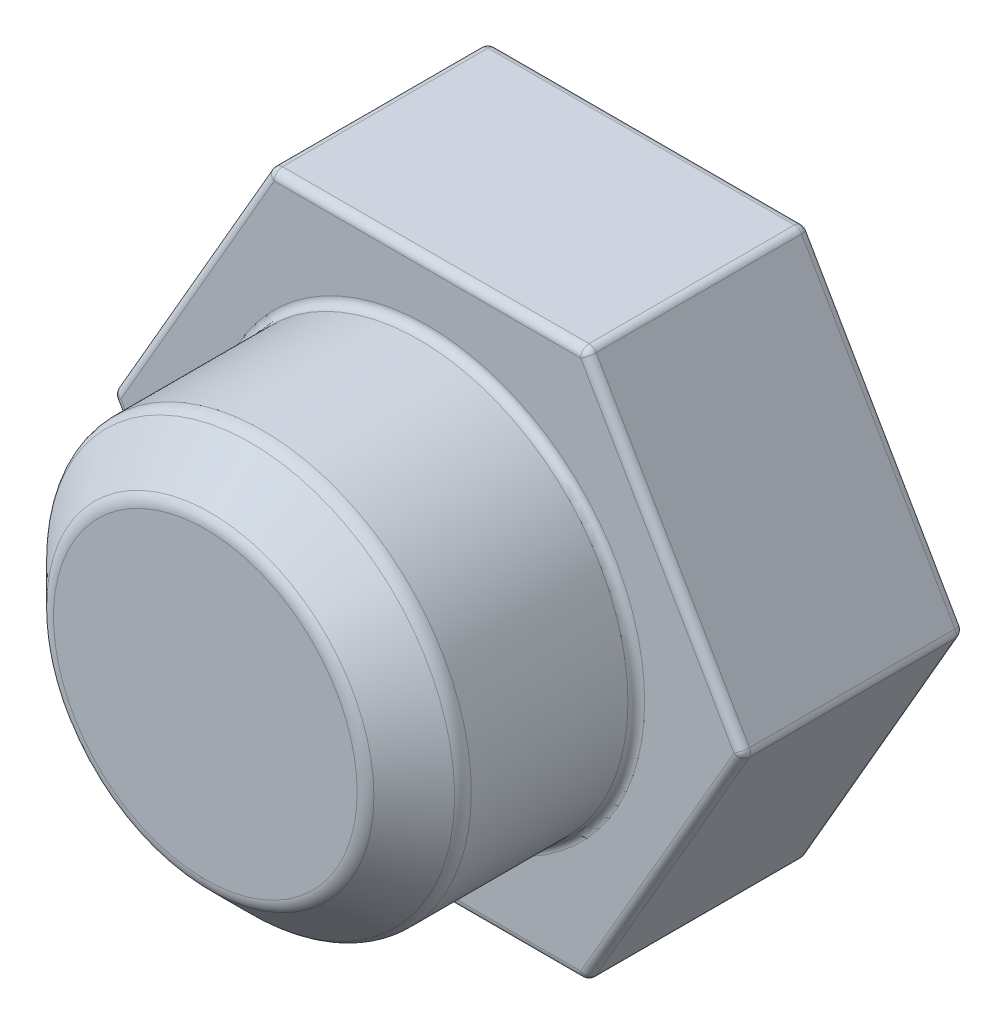
SolidWorks part; units mm, degrees
material "moto_black"
ref_plane "Front Plane" through (0, 0, 0) normal (0, 0, 1) x (1, 0, 0)
ref_plane "Top Plane" through (0, 0, 0) normal (0, 1, 0) x (1, 0, 0)
ref_plane "Right Plane" through (0, 0, 0) normal (1, 0, 0) x (0, 0, -1)
sketch "Sketch1" plane through (0, 0, 0) normal (0, 0, 1) x (1, 0, 0)
  line L1 (18.9181, 0) -> (9.459, 16.3835)
  line L2 (9.459, 16.3835) -> (-9.459, 16.3835)
  line L3 (-9.459, 16.3835) -> (-18.9181, 0)
  line L4 (-18.9181, 0) -> (-9.459, -16.3835)
  line L5 (-9.459, -16.3835) -> (9.459, -16.3835)
  line L6 (9.459, -16.3835) -> (18.9181, 0)
  circle A0 centre (0, 0) radius 16.3835 construction
  circle A1 centre (0, 0) radius 12.5
  dimension "D1" = 25
extrude "Boss-Extrude1" add sketch "Sketch1" against normal blind 13.29
sketch "Sketch2" plane through (0, 0, 0) normal (0, 0, 1) x (1, 0, 0)
  circle A0 centre (0, 0) radius 12.5
  dimension "D1" = 25
extrude "Boss-Extrude2" add sketch "Sketch2" against normal blind 13
extrude "Boss-Extrude3" add sketch "Sketch2<2>" along normal blind 13.29
sketch "Sketch2<2>" plane through (0, 0, 0) normal (0, 0, 1) x (1, 0, 0) same geometry as "Sketch2"
chamfer "Chamfer1" distance 3 angle 45 1 edges at (12.5, 0, 13.29)
fillet "Fillet1" radius 1 2 edges at (9.5, 0, 13.29) (12.5, 0, 10.29)
fillet "Fillet2" radius 0.5 19 edges at (9.459, -16.3835, -6.645) (-9.459, -16.3835, -6.645) (0, -16.3835, 0) (-14.1885, -8.1918, 0) (14.1885, -8.1918, 0) (-14.1885, -8.1918, -13.29) (0, -16.3835, -13.29) (14.1885, -8.1918, -13.29) (12.5, 0, -13.29) (-18.9181, 0, -6.645) (-14.1885, 8.1918, -13.29) (-14.1885, 8.1918, 0) (-9.459, 16.3835, -6.645) (0, 16.3835, -13.29) (0, 16.3835, 0) (9.459, 16.3835, -6.645) (14.1885, 8.1918, -13.29) (18.9181, 0, -6.645) (14.1885, 8.1918, 0)
fillet "Fillet3" radius 0.5 1 edges at (12.5, 0, 0)
